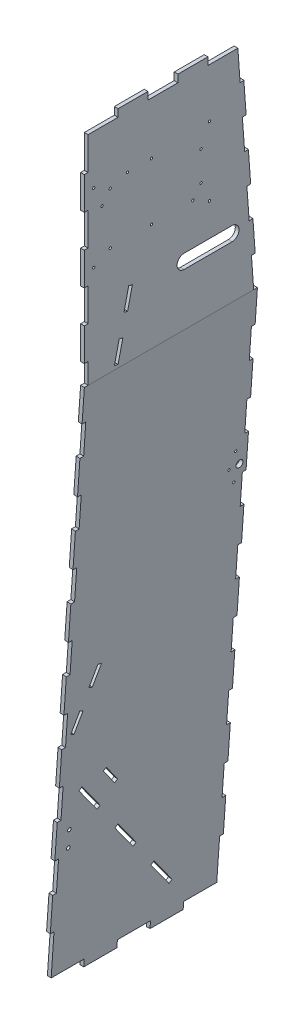
SolidWorks part; units mm, degrees
material "A-Glass Fiber"
ref_plane "Front Plane" through (0, 0, 0) normal (0, 0, 1) x (1, 0, 0)
ref_plane "Top Plane" through (0, 0, 0) normal (0, 1, 0) x (1, 0, 0)
ref_plane "Right Plane" through (0, 0, 0) normal (1, 0, 0) x (0, 0, -1)
sketch "Sketch1" plane through (0, 0, 0) normal (0, 0, 1) x (1, 0, 0)
  line L0 (-215.8818, 2052.32) -> (-215.8818, 1463.04)
  line L1 (-215.8818, 1463.04) -> (-316.0886, 20.32)
  line L2 (-316.0886, 20.32) -> (-317.5, 0)
  line L4 (-215.8818, 2052.32) -> (-215.8818, 2072.64)
  line L6 (-215.8818, 2072.64) -> (-205.7153, 2072.64)
  line L7 (-205.7153, 2072.64) -> (-205.7153, 1463.04)
  line L8 (-205.7153, 1463.04) -> (-307.3335, 0)
  line L9 (-317.5, 0) -> (-307.3335, 0)
  line L10 (-375.4283, 0) -> (-280.9748, 0) construction
  line L13 (-375.4283, 20.32) -> (-280.9748, 20.32) construction
  line L15 (-205.7153, 1463.04) -> (205.7153, 1463.04) construction
  point P3 (0, 0)
  point P23 (-305.9221, 20.32)
  dimension "D1" = 307.3335
extrude "Boss-Extrude1" add sketch "Sketch1" against normal blind 469.9
sketch "Sketch2" plane through (-315.9757, 21.9467, 0) normal (-0.9976, 0.0693, 0) x (0, 0, 1)
  line L35 (0, 1355.6785) -> (0, 0.1049)
  line L37 (-234.95, 1444.5652) -> (-234.95, -21.9996) construction
  line L40 (-10.16, 0.1049) -> (0, 0.1049)
  line L43 (-10.16, 0.1049) -> (-10.16, -21.9996)
  line L46 (0, 1272.0274) -> (-10.16, 1272.0274)
  line L47 (-10.16, 1355.6785) -> (-10.16, 1272.0274)
  line L48 (0, 1355.6785) -> (-10.16, 1355.6785)
  line L49 (0, 1177.9051) -> (-10.16, 1177.9051)
  line L50 (-10.16, 1177.9051) -> (-10.16, 1094.2274)
  line L51 (0, 1094.2274) -> (-10.16, 1094.2274)
  line L52 (0, 916.4274) -> (-10.16, 916.4274)
  line L53 (-10.16, 1000.1317) -> (-10.16, 916.4274)
  line L54 (0, 1000.1317) -> (-10.16, 1000.1317)
  line L55 (0, 822.3583) -> (-10.16, 822.3583)
  line L56 (0, 738.6274) -> (-10.16, 738.6274)
  line L57 (-10.16, 822.3583) -> (-10.16, 738.6274)
  line L58 (0, 644.5849) -> (-10.16, 644.5849)
  line L59 (-10.16, 644.5849) -> (-10.16, 560.8274)
  line L60 (0, 560.8274) -> (-10.16, 560.8274)
  line L61 (0, 466.8115) -> (-10.16, 466.8115)
  line L62 (-10.16, 466.8115) -> (-10.16, 383.0274)
  line L63 (0, 383.0274) -> (-10.16, 383.0274)
  line L64 (0, 289.0381) -> (-10.16, 289.0381)
  line L65 (-10.16, 289.0381) -> (-10.16, 205.2274)
  line L66 (0, 205.2274) -> (-10.16, 205.2274)
  line L67 (0, 111.2647) -> (-10.16, 111.2647)
  line L68 (-10.16, 111.2647) -> (-10.16, 0.1049)
  line L69 (0, 0.1049) -> (-10.16, 0.1049)
  line L70 (-10.16, -21.9996) -> (0, -21.9996)
  line L71 (0, 0.1049) -> (0, -21.9996)
  line L72 (-469.9, 1444.5652) -> (0, 1444.5652) construction
  line L73 (-469.9, -21.9996) -> (0, -21.9996) construction
  line L74 (-469.9, 0.1049) -> (-469.9, -21.9996)
  line L75 (-459.74, -21.9996) -> (-469.9, -21.9996)
  line L76 (-469.9, 0.1049) -> (-459.74, 0.1049)
  line L77 (-459.74, 111.2647) -> (-459.74, 0.1049)
  line L78 (-469.9, 111.2647) -> (-459.74, 111.2647)
  line L79 (-469.9, 205.2274) -> (-459.74, 205.2274)
  line L80 (-459.74, 289.0381) -> (-459.74, 205.2274)
  line L81 (-469.9, 289.0381) -> (-459.74, 289.0381)
  line L82 (-469.9, 383.0274) -> (-459.74, 383.0274)
  line L83 (-459.74, 466.8115) -> (-459.74, 383.0274)
  line L84 (-469.9, 466.8115) -> (-459.74, 466.8115)
  line L85 (-469.9, 560.8274) -> (-459.74, 560.8274)
  line L86 (-459.74, 644.5849) -> (-459.74, 560.8274)
  line L87 (-469.9, 644.5849) -> (-459.74, 644.5849)
  line L88 (-459.74, 822.3583) -> (-459.74, 738.6274)
  line L89 (-469.9, 738.6274) -> (-459.74, 738.6274)
  line L90 (-469.9, 822.3583) -> (-459.74, 822.3583)
  line L91 (-469.9, 1000.1317) -> (-459.74, 1000.1317)
  line L92 (-459.74, 1000.1317) -> (-459.74, 916.4274)
  line L93 (-469.9, 916.4274) -> (-459.74, 916.4274)
  line L94 (-469.9, 1094.2274) -> (-459.74, 1094.2274)
  line L95 (-459.74, 1177.9051) -> (-459.74, 1094.2274)
  line L96 (-469.9, 1177.9051) -> (-459.74, 1177.9051)
  line L97 (-469.9, 1355.6785) -> (-459.74, 1355.6785)
  line L98 (-459.74, 1355.6785) -> (-459.74, 1272.0274)
  line L99 (-469.9, 1272.0274) -> (-459.74, 1272.0274)
  line L100 (-459.74, 0.1049) -> (-459.74, -21.9996)
  line L101 (-459.74, 0.1049) -> (-469.9, 0.1049)
  line L102 (-469.9, 1355.6785) -> (-469.9, 0.1049)
  line L103 (-469.9, 1444.5652) -> (-469.9, -21.9996) construction
  line L104 (-459.74, 205.2274) -> (-469.9, 205.2274) construction
  line M1 (0, -21.9996) -> (0, 1444.5652)
  line M3 (-469.9, 1444.5652) -> (-469.9, -21.9996)
  line M4 (-469.9, -21.9996) -> (0, -21.9996)
extrude "Cut-Extrude1" cut sketch "Sketch2" against normal blind 10.16 contours L66 L35 L64 L65 | L69 L67 L68 M1 | L60 L35 L58 L59 | L63 L35 L61 L62 | L55 L57 L56 L35 | L35 L54 L53 L52 | L51 L35 L49 L50 | L35 L48 L47 L46 | L40 L43 M4 M1 | L100 L76 M3 M4 | L78 L76 L77 M3 | L81 L79 L80 M3 | L84 L82 L83 M3 | L87 L85 L86 M3 | L90 L89 L88 M3 | L93 L92 L91 M3 | L96 L94 L95 M3 | L99 L98 L97 M3 region at (-224.9388, 1332.6419, -464.82) region at (-237.2577, 1155.2825, -464.82) region at (-249.5765, 977.9231, -464.82) region at (-261.8953, 800.5637, -464.82) region at (-274.2142, 623.2043, -464.82) region at (-286.533, 445.8449, -464.82) region at (-298.8518, 268.4855, -464.82) region at (-316.7342, 11.0257, -464.82) region at (-312.1173, 77.4977, -5.08) region at (-298.8518, 268.4855, -5.08) region at (-286.533, 445.8449, -5.08) region at (-274.2142, 623.2043, -5.08) region at (-261.8953, 800.5637, -5.08) region at (-249.5765, 977.9231, -5.08) region at (-237.2577, 1155.2825, -5.08) region at (-224.9388, 1332.6419, -5.08) region at (-316.7342, 11.0257, -5.08) region at (-312.1173, 77.4977, -464.82)
sketch "Sketch3" plane through (-215.8818, 0, 0) normal (-1, 0, 0) x (0, 0, 1)
  line L0 (0, 2052.32) -> (-10.16, 2052.32) construction
  line L1 (0, 1963.42) -> (-10.16, 1963.42) construction
  line L2 (-10.16, 2052.32) -> (-10.16, 1963.42) construction
  line L3 (0, 1874.52) -> (-10.16, 1874.52) construction
  line L4 (0, 1463.04) -> (0, 2072.64)
  line L5 (0, 2072.64) -> (-469.9, 2072.64)
  line L6 (-469.9, 2072.64) -> (-469.9, 1463.04)
  line L8 (0, 1463.04) -> (0, 2072.64)
  line L9 (0, 2072.64) -> (-469.9, 2072.64)
  line L12 (0, 1785.62) -> (-10.16, 1785.62) construction
  line L13 (-10.16, 1874.52) -> (-10.16, 1785.62) construction
  line L14 (0, 1696.72) -> (-10.16, 1696.72) construction
  line L15 (0, 1607.82) -> (-10.16, 1607.82) construction
  line L16 (-10.16, 1696.72) -> (-10.16, 1607.82) construction
  line L17 (0, 1518.92) -> (-10.16, 1518.92) construction
  line L18 (-10.16, 1518.92) -> (-10.16, 1488.44) construction
  line L19 (0, 2052.32) -> (-10.16, 2052.32)
  line L20 (0, 1963.42) -> (-10.16, 1963.42)
  line L21 (-10.16, 2052.32) -> (-10.16, 1963.42)
  line L22 (0, 1874.52) -> (-10.16, 1874.52)
  line L23 (0, 1785.62) -> (-10.16, 1785.62)
  line L24 (-10.16, 1874.52) -> (-10.16, 1785.62)
  line L25 (0, 1696.72) -> (-10.16, 1696.72)
  line L26 (0, 1607.82) -> (-10.16, 1607.82)
  line L27 (-10.16, 1696.72) -> (-10.16, 1607.82)
  line L28 (0, 1518.92) -> (-10.16, 1518.92)
  line L29 (-10.16, 1518.92) -> (-10.16, 1488.44)
  line L30 (0, 2052.32) -> (0, 1463.04)
  line L31 (-234.95, 1463.04) -> (-234.95, 2072.64) construction
  line L32 (-10.16, 2052.32) -> (0, 2052.32)
  line L33 (-10.16, 2052.32) -> (-10.16, 2072.64)
  line L34 (-10.16, 2072.64) -> (0, 2072.64)
  line L35 (0, 2052.32) -> (0, 2072.64)
  line L36 (-469.9, 1463.04) -> (-425.45, 2072.64)
  line L37 (-469.9, 1463.04) -> (-463.754, 1547.3284)
  line L38 (-469.9, 1463.04) -> (-459.7669, 1462.3011)
  line L39 (-463.754, 1547.3284) -> (-453.6209, 1546.5895)
  line L40 (-459.7669, 1462.3011) -> (-453.6209, 1546.5895)
  line L41 (-463.754, 1547.3284) -> (-453.6209, 1546.5895)
  line L42 (-463.754, 1547.3284) -> (-457.6079, 1631.6168)
  line L43 (-453.6209, 1546.5895) -> (-447.4748, 1630.8779)
  line L44 (-457.6079, 1631.6168) -> (-447.4748, 1630.8779)
  line L45 (-457.6079, 1631.6168) -> (-447.4748, 1630.8779)
  line L46 (-457.6079, 1631.6168) -> (-451.4619, 1715.9052)
  line L47 (-447.4748, 1630.8779) -> (-441.3288, 1715.1664)
  line L48 (-451.4619, 1715.9052) -> (-441.3288, 1715.1664)
  line L49 (-451.4619, 1715.9052) -> (-441.3288, 1715.1664)
  line L50 (-451.4619, 1715.9052) -> (-445.3159, 1800.1936)
  line L51 (-441.3288, 1715.1664) -> (-435.1828, 1799.4548)
  line L52 (-445.3159, 1800.1936) -> (-435.1828, 1799.4548)
  line L53 (-445.3159, 1800.1936) -> (-435.1828, 1799.4548)
  line L54 (-10.16, 1488.44) -> (-10.16, 1463.04)
  line L56 (-445.3159, 1800.1936) -> (-439.1699, 1884.4821)
  line L57 (-435.1828, 1799.4548) -> (-429.0368, 1883.7432)
  line L58 (-439.1699, 1884.4821) -> (-429.0368, 1883.7432)
  line L59 (-439.1699, 1884.4821) -> (-429.0368, 1883.7432)
  line L60 (-439.1699, 1884.4821) -> (-433.0238, 1968.7705)
  line L61 (-429.0368, 1883.7432) -> (-422.8907, 1968.0316)
  line L62 (-433.0238, 1968.7705) -> (-422.8907, 1968.0316)
  line L63 (-10.16, 2052.32) -> (-469.9, 2052.32) construction
  line L64 (-469.9, 2072.64) -> (-469.9, 1463.04) construction
  line L65 (-433.0238, 1968.7705) -> (-422.8907, 1968.0316)
  line L66 (-433.0238, 1968.7705) -> (-426.8778, 2053.0589)
  line L67 (-422.8907, 1968.0316) -> (-416.7447, 2052.32)
  line L68 (-426.8778, 2053.0589) -> (-416.7447, 2052.32)
  line L69 (-416.7447, 2052.32) -> (-426.9317, 2052.32)
  line L70 (-426.8778, 2053.0589) -> (-416.7447, 2052.32)
  line L71 (-426.8778, 2053.0589) -> (-425.3531, 2073.9694)
  line L72 (-416.7447, 2052.32) -> (-415.22, 2073.2306)
  line L73 (-425.3531, 2073.9694) -> (-415.22, 2073.2306)
  line L74 (-469.9, 1463.04) -> (0, 1463.04) construction
  line L75 (-10.16, 1488.44) -> (-10.16, 20.32) construction
  line L78 (-469.9, 1463.04) -> (0, 1463.04)
  line L79 (-469.9, 1463.04) -> (0, 1463.04)
  line M7 (0, 1463.04) -> (0, 2072.64)
  line M8 (0, 2072.64) -> (-469.9, 2072.64)
  line M9 (-469.9, 2072.64) -> (-469.9, 1463.04)
  line M10 (-469.9, 1463.04) -> (0, 1463.04)
  dimension "D2" = 44.45
  dimension "D3" = 10.16
  dimension "D1" = 0
extrude "Cut-Extrude2" cut sketch "Sketch3" against normal blind 12.7 contours M10 | L29 L54 L28 M10 M7 | L36 L66 M9 M8 | L48 L36 L44 L47 | L58 L36 L52 L57 | L67 L69 L36 L62 | L25 L27 L26 L8 | L22 L24 L23 L8 | L19 L21 L20 L8 | L33 L19 L8 M8 | L68 L72 L36 M8 | L69 L68 L66 region at (-215.8818, 1490.98, -5.08) region at (-215.8818, 1652.27, -5.08) region at (-215.8818, 1504.9998, -461.7544) region at (-215.8818, 1869.44, -455.0833) region at (-215.8818, 1830.07, -5.08) region at (-215.8818, 1673.3916, -449.4684) region at (-215.8818, 2062.6636, -421.0525) region at (-215.8818, 2007.87, -5.08) region at (-215.8818, 1841.9684, -437.1763) region at (-215.8818, 2052.5663, -423.5181) region at (-215.8818, 2062.48, -5.08) region at (-215.8818, 2010.3602, -424.8903)
sketch "Sketch4" plane through (-215.8818, 0, 0) normal (-1, 0, 0) x (0, 0, 1)
  line L1 (-416.7447, 2072.64) -> (-335.4278, 2072.64)
  line L2 (-416.7447, 2072.64) -> (-416.7447, 2052.32)
  line L3 (-416.7447, 2052.32) -> (-335.4278, 2052.32)
  line L4 (-335.4278, 2072.64) -> (-335.4278, 2052.32)
  line L5 (-10.16, 2072.64) -> (-10.16, 1963.42) construction
  line L6 (-335.4278, 2072.64) -> (-254.1108, 2072.64)
  line L7 (-335.4278, 2072.64) -> (-335.4278, 2052.32)
  line L8 (-335.4278, 2052.32) -> (-254.1108, 2052.32)
  line L9 (-254.1108, 2072.64) -> (-254.1108, 2052.32)
  line L10 (-254.1108, 2072.64) -> (-172.7939, 2072.64)
  line L11 (-254.1108, 2072.64) -> (-254.1108, 2052.32)
  line L12 (-254.1108, 2052.32) -> (-172.7939, 2052.32)
  line L13 (-172.7939, 2072.64) -> (-172.7939, 2052.32)
  line L14 (-172.7939, 2072.64) -> (-91.4769, 2072.64)
  line L15 (-172.7939, 2072.64) -> (-172.7939, 2052.32)
  line L16 (-172.7939, 2052.32) -> (-91.4769, 2052.32)
  line L17 (-91.4769, 2072.64) -> (-91.4769, 2052.32)
  line L18 (-91.4769, 2072.64) -> (-10.16, 2072.64)
  line L19 (-91.4769, 2072.64) -> (-91.4769, 2052.32)
  line L20 (-91.4769, 2052.32) -> (-10.16, 2052.32)
  line L21 (-10.16, 2072.64) -> (-10.16, 2052.32)
  line L23 (-422.8907, 1968.0316) -> (-415.263, 2072.64) construction
  line L24 (-415.263, 2072.64) -> (-10.16, 2072.64) construction
  point P4 (0, 0)
  point P5 (0, 0)
  point P19 (0, 0)
  point P20 (0, 0)
  point P21 (0, 0)
  line M26 (-10.16, 1963.42) -> (-10.16, 2072.64)
  line M27 (-10.16, 2072.64) -> (-415.263, 2072.64)
  dimension "D1" = 20.32
extrude "Cut-Extrude3" cut sketch "Sketch4" against normal blind 12.7 contours L4 L3 M27 | L13 L9 L12 M27 | L17 L20 M26 M27 region at (-215.8818, 2062.48, -376.0862) region at (-215.8818, 2062.48, -213.4523) region at (-215.8818, 2062.48, -50.8185)
sketch "Sketch5" plane through (-315.9757, 21.9467, 0) normal (-0.9976, 0.0693, 0) x (0, 0, 1)
  line L1 (-459.74, -21.9996) -> (-369.824, -21.9996)
  line L2 (-459.74, -21.9996) -> (-459.74, -1.6796)
  line L3 (-459.74, -1.6796) -> (-369.824, -1.6796)
  line L4 (-369.824, -21.9996) -> (-369.824, -1.6796)
  line L5 (-369.824, -21.9996) -> (-279.908, -21.9996)
  line L6 (-369.824, -21.9996) -> (-369.824, -1.6796)
  line L7 (-369.824, -1.6796) -> (-279.908, -1.6796)
  line L8 (-279.908, -21.9996) -> (-279.908, -1.6796)
  line L9 (-279.908, -21.9996) -> (-189.992, -21.9996)
  line L10 (-279.908, -21.9996) -> (-279.908, -1.6796)
  line L11 (-279.908, -1.6796) -> (-189.992, -1.6796)
  line L12 (-189.992, -21.9996) -> (-189.992, -1.6796)
  line L13 (-189.992, -21.9996) -> (-100.076, -21.9996)
  line L14 (-189.992, -21.9996) -> (-189.992, -1.6796)
  line L15 (-189.992, -1.6796) -> (-100.076, -1.6796)
  line L16 (-100.076, -21.9996) -> (-100.076, -1.6796)
  line L17 (-100.076, -21.9996) -> (-10.16, -21.9996)
  line L18 (-100.076, -21.9996) -> (-100.076, -1.6796)
  line L19 (-100.076, -1.6796) -> (-10.16, -1.6796)
  line L20 (-10.16, -21.9996) -> (-10.16, -1.6796)
  line L21 (-10.16, 111.2647) -> (-10.16, -21.9996) construction
  dimension "D1" = 20.32
extrude "Cut-Extrude4" cut sketch "Sketch5" against normal blind 12.7 contours L1 L4 L3 L2 | L9 L12 L11 L8 | L17 L20 L19 L18 L16 region at (-316.796, 10.1356, -414.782) region at (-316.796, 10.1356, -234.95) region at (-316.796, 10.1356, -55.118)
sketch "Sketch6" plane through (-315.9757, 21.9467, 0) normal (-0.9976, 0.0693, 0) x (0, 0, 1)
  line L0 (-217.3726, 211.9965) -> (-163.4402, 285.2141)
  line L1 (-325.2304, 65.5562) -> (-271.298, 138.7738)
  line L2 (-44.1085, 632.6765) -> (-22.5289, 586.4358) construction
  line L3 (-74.8989, 674.6188) -> (-65.6881, 678.9173) construction
  line L8 (-271.6486, 139.032) -> (-279.8219, 145.0526) construction
  line L56 (-87.2678, 725.158) -> (-65.6881, 678.9173) construction
  line L57 (-74.8989, 674.6188) -> (-96.4785, 720.8595) construction
  line L58 (-31.7396, 582.1373) -> (-22.5289, 586.4358) construction
  line L59 (-31.7396, 582.1373) -> (-53.3192, 628.3781) construction
  line L60 (-53.3192, 628.3781) -> (-44.1085, 632.6765) construction
  line L63 (-117.6881, 364.4573) -> (-63.7557, 437.6749) construction
  line L65 (-225.5528, 218.0222) -> (-171.6205, 291.2397) construction
  line L69 (-333.4176, 71.587) -> (-279.4852, 144.8046) construction
  line L70 (-109.5008, 358.4266) -> (-55.5685, 431.6442)
  line L71 (-44.1085, 632.6765) -> (-22.5289, 586.4358)
  line L72 (-74.8989, 674.6188) -> (-65.6881, 678.9173)
  line L73 (-87.2678, 725.158) -> (-65.6881, 678.9173)
  line L74 (-74.8989, 674.6188) -> (-96.4785, 720.8595)
  line L75 (-31.7396, 582.1373) -> (-22.5289, 586.4358)
  line L76 (-31.7396, 582.1373) -> (-53.3192, 628.3781)
  line L77 (-53.3192, 628.3781) -> (-44.1085, 632.6765)
  line L78 (-109.5008, 358.4266) -> (-117.6881, 364.4573)
  line L79 (-55.5685, 431.6442) -> (-63.7557, 437.6749)
  line L80 (-117.6881, 364.4573) -> (-63.7557, 437.6749)
  line L81 (-163.4402, 285.2141) -> (-171.6205, 291.2397)
  line L82 (-225.5528, 218.0222) -> (-171.6205, 291.2397)
  line L83 (-217.3726, 211.9965) -> (-225.5528, 218.0222)
  line L84 (-271.298, 138.7738) -> (-279.4852, 144.8046)
  line L85 (-325.2304, 65.5562) -> (-333.4176, 71.587)
  line L86 (-333.4176, 71.587) -> (-279.4852, 144.8046)
  line L87 (-87.2678, 725.158) -> (-96.4785, 720.8595)
  line L89 (-109.8514, 358.6848) -> (-118.0248, 364.7053) construction
  line L90 (-163.7838, 285.4672) -> (-171.9572, 291.4877) construction
  line L91 (-217.7162, 212.2496) -> (-225.8895, 218.2702) construction
  dimension "D1" = 10.16
extrude "Cut-Extrude5" cut sketch "Sketch6" against normal blind 137.414 contours L73 L87 L74 L72 | L77 L76 L75 L71 | L80 L78 | L83 L81 L82 | L86 L85 L84 region at (-298.541, 272.9601, -194.4965) region at (-308.6877, 126.8743, -302.3578) region at (-288.3947, 419.0407, -86.6283) region at (-273.8885, 627.8938, -37.9241) region at (-267.4804, 720.1529, -81.0833)
sketch "Sketch8" plane through (-215.8818, 0, 0) normal (-1, 0, 0) x (0, 0, 1)
  circle A0 centre (-450.215, 1043.94) radius 9.525 construction
  circle A1 centre (-450.215, 1043.94) radius 9.525
extrude "Cut-Extrude7" cut sketch "Sketch8" along normal through all
sketch "Sketch13" plane through (-215.8818, 0, 0) normal (-1, 0, 0) x (0, 0, 1)
  line L0 (-413.556, 1633.6344) -> (-413.556, 1614.5844)
  line L1 (-270.8715, 1611.4094) -> (-270.8715, 1636.8094)
  line L2 (-413.556, 1624.1094) -> (-270.8715, 1624.1094) construction
  line L3 (-270.8715, 1624.1094) -> (-400.856, 1624.1094) construction
  line L4 (-270.8715, 1605.0594) -> (-400.856, 1605.0594)
  line L5 (-270.8715, 1643.1594) -> (-400.856, 1643.1594)
  line L6 (-416.7447, 2052.32) -> (-335.4278, 2052.32)
  line L7 (-422.8907, 1968.0316) -> (-416.7447, 2052.32)
  circle A0 centre (-25.2465, 1731.87) radius 3.175
  circle A1 centre (-70.409, 1755.42) radius 3.175
  circle A2 centre (-182.409, 1755.42) radius 3.175
  circle A3 centre (-25.2465, 1918.97) radius 3.175
  circle A4 centre (-47.789, 1865.42) radius 3.175
  circle A5 centre (-182.409, 1910.42) radius 3.175
  circle A6 centre (-117.079, 1910.42) radius 3.175
  circle A7 centre (-70.409, 1895.42) radius 3.175
  circle A8 centre (-317.029, 1865.42) radius 3.175
  circle A9 centre (-294.409, 1755.42) radius 3.175
  circle A10 centre (-317.029, 1785.42) radius 3.175
  circle A11 centre (-339.5715, 1731.87) radius 3.175
  circle A12 centre (-339.5715, 1918.97) radius 3.175
  arc A13 (-270.8715, 1605.0594) -> (-270.8715, 1643.1594) centre (-270.8715, 1624.1094) ccw
  arc A14 (-400.856, 1643.1594) -> (-400.856, 1605.0594) centre (-400.856, 1624.1094) ccw
  point P34 (-335.8637, 1624.1094)
  point P42 (-416.7447, 2052.32)
  dimension "D1" = 12.7
  dimension "D2" = 19.05
extrude "Cut-Extrude8" cut sketch "Sketch13" against normal through all contours L5 A14 L4 A13 | A11 | A10 | A9 | A2 | A1 | A0 | A4 | A7 | A6 | A3 | A5 | A8 | A12 | L0 A14 region at (-215.8818, 1624.1094, -335.8637) region at (-215.8818, 1731.87, -25.2465) region at (-215.8818, 1755.42, -70.409) region at (-215.8818, 1755.42, -182.409) region at (-215.8818, 1918.97, -25.2465) region at (-215.8818, 1865.42, -47.789) region at (-215.8818, 1910.42, -182.409) region at (-215.8818, 1910.42, -117.079) region at (-215.8818, 1895.42, -70.409) region at (-215.8818, 1865.42, -317.029) region at (-215.8818, 1755.42, -294.409) region at (-215.8818, 1785.42, -317.029) region at (-215.8818, 1731.87, -339.5715) region at (-215.8818, 1918.97, -339.5715)
sketch "Sketch17" plane through (-215.8818, 0, 0) normal (-1, 0, 0) x (0, 0, 1)
  line L0 (-130.4243, 1639.6605) -> (-120.5247, 1641.946)
  line L1 (-120.5247, 1641.946) -> (-107.584, 1585.8939)
  line L2 (-130.4243, 1639.6605) -> (-117.4836, 1583.6084)
  line L3 (-117.4836, 1583.6084) -> (-107.584, 1585.8939)
  line L4 (-104.543, 1527.5563) -> (-94.6434, 1529.8418)
  line L5 (-91.6023, 1471.5043) -> (-104.543, 1527.5563)
  line L6 (-91.6023, 1471.5043) -> (-81.7027, 1473.7898)
  line L7 (-81.7027, 1473.7898) -> (-94.6434, 1529.8418)
  line L8 (-416.7447, 2052.32) -> (-335.4278, 2052.32)
  line L9 (-422.8907, 1968.0316) -> (-416.7447, 2052.32)
  point P11 (-416.7447, 2052.32)
extrude "Cut-Extrude9" cut sketch "Sketch17" against normal through all contours L6 L7 L4 L5 | L2 L3 L1 L0 region at (-215.8818, 1612.7772, -119.0041) region at (-215.8818, 1500.6731, -93.1229)
sketch "Sketch20" plane through (-315.9757, 21.9467, 0) normal (-0.9976, 0.0693, 0) x (0, 0, 1)
  line L0 (-441.6805, 375.8656) -> (-258.1103, 563.7707)
  line L1 (-258.1103, 563.7707) -> (-341.7803, 797.9819)
  line L2 (-258.1103, 563.7707) -> (-10.16, 315.8204)
  line L3 (-258.1103, 563.7707) -> (-258.6478, 797.9819)
  line L8 (-10.16, 110.1771) -> (-10.16, -1.6796)
  line L9 (-10.16, 466.8115) -> (-10.16, 383.0274) construction
  line L10 (-13.335, 290.1376) -> (-13.335, 359.9876)
  line L11 (-13.335, 290.1376) -> (-48.26, 290.1376)
  line L12 (-13.335, 359.9876) -> (-48.26, 359.9876)
  line L13 (-48.26, 290.1376) -> (-48.26, 359.9876)
  line L32 (-120.9293, 445.7124) -> (-154.8235, 399.6982)
  line L33 (-120.9293, 445.7124) -> (-128.5983, 451.3614)
  line L34 (-154.8235, 399.6982) -> (-162.4926, 405.3473)
  line L35 (-128.5983, 451.3614) -> (-162.4926, 405.3473)
  line L37 (-109.5008, 358.4266) -> (-117.6881, 364.4573) construction
  line L38 (-117.6881, 364.4573) -> (-63.7557, 437.6749) construction
  line L39 (-137.8764, 422.7053) -> (43.6586, 288.9858) construction
  line L40 (-35.56, 332.8883) -> (-35.56, 361.687) construction
  line L41 (-10.16, 466.8115) -> (-10.16, 383.0274)
  circle A0 centre (-35.56, 347.2876) radius 4.7625
  circle A2 centre (-35.56, 302.8376) radius 4.7625
  point P11 (-10.16, -1.6796)
  point P57 (-35.56, 341.2204)
  dimension "D9" = 44.45
  dimension "D15" = 9.525
  dimension "D3" = 3.175
  dimension "D4" = 12.7
  dimension "D5" = 57.15
  dimension "D6" = 317.5
  dimension "D7" = 12.7
  dimension "D8" = 12.7
  dimension "D22" = 9.525
  dimension "D23" = 6.35
  dimension "D24" = 50.8
  dimension "D25" = 34.925
extrude "Cut-Extrude10" cut sketch "Sketch20" against normal through all contours A2 | L2 A0 | L2 A0 | L2 L35 L34 L32 | L33 L35 L2 L32 region at (-285.2619, 464.1454, -128.5379) region at (-286.8509, 441.2683, -145.572) region at (-291.908, 368.4591, -35.5004) region at (-292.1316, 365.2395, -38.7278) region at (-294.992, 324.0565, -35.56)
sketch "Sketch22" [suppressed] plane through (-315.9757, 21.9467, 0) normal (-0.9976, 0.0693, 0) x (0, 0, 1)
  line L3 (-138.6114, 421.183) -> (-138.6114, 431.343)
  line L4 (-138.6114, 431.343) -> (-202.8371, 431.343)
  line L5 (-138.6114, 421.183) -> (-202.8371, 421.183)
  line L6 (-202.8371, 421.183) -> (-202.8371, 431.343)
  line L7 (-267.0629, 421.183) -> (-267.0629, 431.343)
  line L8 (-267.0629, 431.343) -> (-331.2886, 431.343)
  line L9 (-267.0629, 421.183) -> (-331.2886, 421.183)
  line L10 (-331.2886, 421.183) -> (-331.2886, 431.343)
  line L11 (-395.5143, 421.183) -> (-395.5143, 431.343)
  line L12 (-395.5143, 421.183) -> (-459.74, 421.183)
  line L13 (-395.5143, 431.343) -> (-459.74, 431.343)
  line L15 (-459.74, 421.183) -> (-459.74, 431.343)
  line L16 (-100.076, -1.6796) -> (-10.16, -1.6796) construction
  line L17 (-10.16, 111.2647) -> (-10.16, -1.6796) construction
  line L18 (-100.076, -1.6796) -> (-10.16, -1.6796)
  line L19 (-10.16, 111.2647) -> (-10.16, -1.6796)
  point P0 (-10.16, -1.6796)
sketch "Sketch23" plane through (-315.9757, 21.9467, 0) normal (-0.9976, 0.0693, 0) x (0, 0, 1)
  line L2 (-450.215, 1024.4555) -> (-396.5689, 1024.4555) construction
  line L3 (-437.515, 986.3555) -> (-437.515, 1062.5555) construction
  circle A0 centre (-437.515, 986.3555) radius 3.175
  circle A1 centre (-421.64, 1024.4555) radius 3.175
  circle A2 centre (-437.515, 1062.5555) radius 3.175
  point P21 (-437.515, 1024.4555)
  dimension "D1" = 6.35
  dimension "D2" = 28.575
  dimension "D3" = 76.2
  dimension "D4" = 12.7
extrude "Cut-Extrude11" cut sketch "Sketch23" against normal through all contours A1 | A0 | A2 region at (-247.6311, 1005.9316, -437.515) region at (-244.9912, 1043.94, -421.64) region at (-242.3512, 1081.9484, -437.515)
